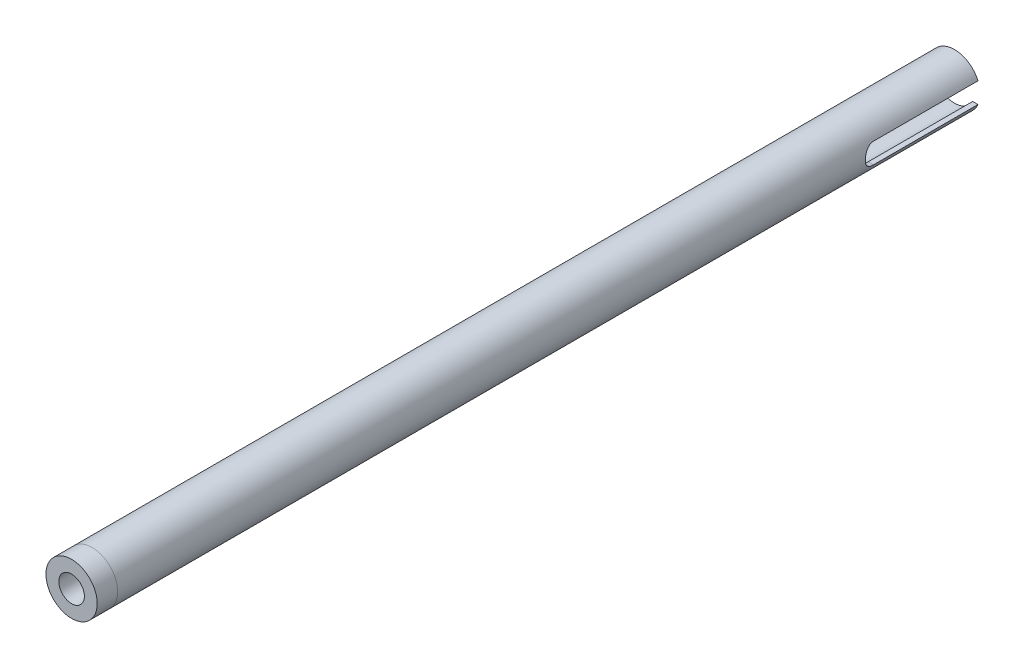
SolidWorks part; units mm, degrees
material "AISI 4130 Steel, annealed at 865C"
ref_plane "Front Plane" through (0, 0, 0) normal (0, 0, 1) x (1, 0, 0)
ref_plane "Top Plane" through (0, 0, 0) normal (0, 1, 0) x (1, 0, 0)
ref_plane "Right Plane" through (0, 0, 0) normal (1, 0, 0) x (0, 0, -1)
sketch "Axis" plane through (0, 0, 0) normal (0, 1, 0) x (1, 0, 0)
  line L0 (0, 0) -> (0, 273.4854) construction
  line L1 (0, 0) -> (0, -28.575) construction
  line L2 (0, 273.4854) -> (-7.9375, 273.4854) construction
  line L3 (0, 294.3429) -> (-10.3187, 267.2281) construction
  dimension "D1" = 28.575
  dimension "D2" = 7.9375
sketch "Sketch1" plane through (0, 0, 0) normal (0, 0, 1) x (1, 0, 0)
  line L0 (-7.9375, 0) -> (7.9375, 0) construction
  line L1 (-7.2748, 3.175) -> (7.2748, 3.175)
  line L2 (-7.2748, -3.175) -> (7.2748, -3.175)
  circle A0 centre (0, 0) radius 7.9375
  circle A1 centre (0, 0) radius 6.4643
  circle A2 centre (0, 0) radius 3.9688
  dimension "D1" = 15.875
  dimension "D3" = 7.9375
  dimension "D2" = 1.4732
  dimension "D4" = 6.35
extrude "Threaded insert 1-1" add sketch "Sketch1" against normal blind 6.35 contours A2 L1 A1 | A1 L1 A0 | A2 L0 A1 L1 | A1 L0 A0 L1 | L0 A1 L2 A0 | L0 A2 L2 A1 | A2 L2 A1 | A1 L2 A0 | L0 A1 L2 A2 | L0 A0 L2 A1 | A0 L0 A1 L1 | A1 L0 A2 L1 region at (4.8156, 1.6537, 0) region at (4.8156, -1.6537, 0) region at (6.9501, 1.6161, 0) region at (6.9501, -1.6161, 0) region at (-4.8156, -1.6537, 0) region at (-4.8156, 1.6537, 0) region at (0, 4.6361, 0) region at (0, -4.6361, 0) region at (0, 6.6174, 0) region at (6.4528, -3.3281, 0) region at (-6.9501, -1.6161, 0) region at (-6.9501, 1.6161, 0)
extrude "Threaded insert 1-2" add sketch "Sketch1<3>" against normal blind 9.525 from surface contours A2 L1 A1 | A2 L0 A1 L1 | L0 A2 L2 A1 | A2 L2 A1 | L0 A1 L2 A2 | A1 L0 A2 L1 region at (4.8156, 1.6537, 0) region at (4.8156, -1.6537, 0) region at (-4.8156, -1.6537, 0) region at (-4.8156, 1.6537, 0) region at (0, 4.6361, 0) region at (0, -4.6361, 0) starting at face at (7.9375, 0, -6.35)
sketch "Sketch1<3>" plane through (0, 0, 0) normal (0, 0, 1) x (1, 0, 0) same geometry as "Sketch1"
extrude "A-arm tube" add sketch "Sketch1<4>" against normal up to vertex (273.4854 mm away) from surface separate body contours A1 L1 A0 | A1 L0 A0 L1 | L0 A1 L2 A0 | A1 L2 A0 | L0 A0 L2 A1 | A0 L0 A1 L1 region at (6.9501, 1.6161, 0) region at (6.9501, -1.6161, 0) region at (0, 6.6174, 0) region at (6.4528, -3.3281, 0) region at (-6.9501, -1.6161, 0) region at (-6.9501, 1.6161, 0) up to point (0, 0, -273.4854) starting at face at (6.4643, 0, -6.35)
sketch "Sketch1<4>" plane through (0, 0, 0) normal (0, 0, 1) x (1, 0, 0) same geometry as "Sketch1"
extrude "Apex slot" cut sketch "Sketch1<5>" along normal blind 35.56 from surface contours A0 L0 A1 L1 | L0 A0 L2 A1 | A1 L0 A0 L1 | L0 A1 L2 A0 region at (6.9501, 1.6161, 0) region at (6.9501, -1.6161, 0) region at (-6.9501, -1.6161, 0) region at (-6.9501, 1.6161, 0) starting at face at (6.4643, 0, -273.4854)
sketch "Sketch1<5>" plane through (0, 0, 0) normal (0, 0, 1) x (1, 0, 0) same geometry as "Sketch1"
fillet "Fillet1" radius 3.175 4 edges at (-6.4528, 3.175, -237.9254) (-6.4528, -3.175, -237.9254) (6.4528, -3.175, -237.9254) (6.4528, 3.175, -237.9254)
equation "\"tube diameter\"= 5 / 8"
equation "\"tube thickness\"= .058"
equation "\"apex thickness\"= .25"
equation "\"tube slot\"= 1.4"
equation "\"D1@Sketch1\"=\"tube diameter\""
equation "\"D2@Sketch1\"=\"tube thickness\""
equation "\"threaded insert hole\"= .3125"
equation "\"D3@Sketch1\"=\"threaded insert hole\""
equation "\"D4@Sketch1\"=\"apex thickness\""
equation "\"D1@Apex slot\" = \"tube slot\""
equation "\"D1@Fillet1\"=\"apex thickness\"/2"
